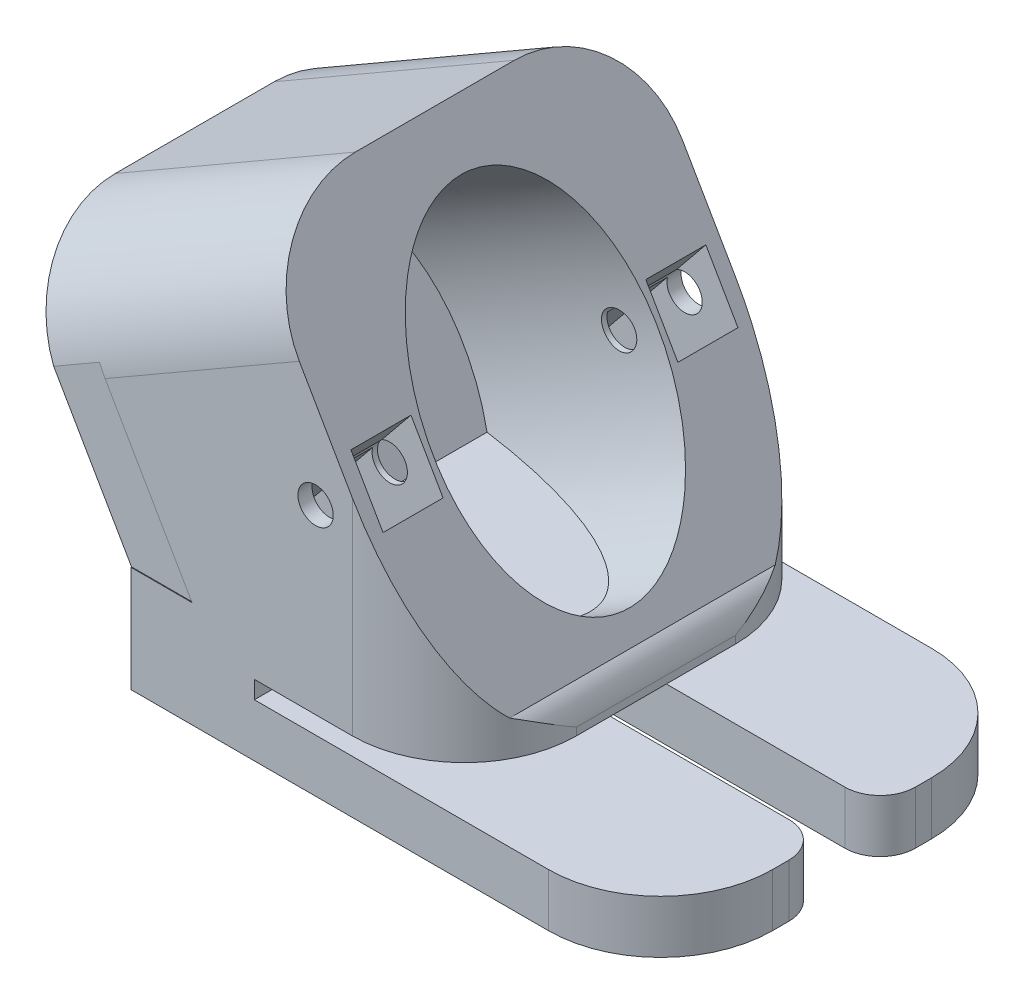
SolidWorks part; units mm, degrees
note: The reader was unsure of these and kept them because the rebuilt part matched: shared geometry of "Sketch7<3>".
ref_plane "Front Plane" through (0, 0, 0) normal (0, 0, 1) x (1, 0, 0)
ref_plane "Top Plane" through (0, 0, 0) normal (0, 1, 0) x (1, 0, 0)
ref_plane "Right Plane" through (0, 0, 0) normal (1, 0, 0) x (0, 0, -1)
sketch "Sketch1" plane through (0, 0, 0) normal (0, 0, 1) x (1, 0, 0)
  line L0 (0, 0) -> (16.4978, 9.525)
  line L1 (0, 0) -> (20.7767, 0) construction
  line L2 (12.7, 0) -> (19.6728, 4.0257)
  line L3 (19.6928, 3.9911) -> (16.4978, 9.525) construction
  point P9 (14.1735, 0.8507)
  dimension "D1" = 19.05
  dimension "D2" = 30
  dimension "D3" = 6.35
  dimension "D4" = 8.0515
  dimension "D5" = 6.35
ref_plane "Plane1" through (16.4978, 9.525, 0) normal (0.866, 0.5, 0) x (0, 0, -1)
sketch "Sketch2" plane through (16.4978, 9.525, 0) normal (0.866, 0.5, 0) x (0, 0, -1)
  line L0 (0, 100000) -> (0, -100010.3884) construction
  line L1 (10.85, 12.525) -> (10.85, -12.525)
  line L2 (10.85, 12.525) -> (-10.85, 12.525)
  line L3 (10.85, -12.525) -> (-10.85, -12.525)
  line L4 (-10.85, 12.525) -> (-10.85, -12.525)
  line L5 (10.85, 12.525) -> (-10.85, -12.525) construction
  line L6 (10.85, -12.525) -> (-10.85, 12.525) construction
  ellipse E0 centre (0, 0) end of major axis (0, 9.525) minor radius 6.35
  point P1 (-10.85, 0)
  point P7 (0, -12.525)
  dimension "D1" = 19.05
  dimension "D2" = 12.7
  dimension "D3" = 4.5
  dimension "D4" = 3
extrude "Boss-Extrude1" add sketch "Sketch2" against normal blind 12.7
sketch "Sketch3" plane through (5.4993, 3.175, 0) normal (-0.866, -0.5, 0) x (0, 0, 1)
  line L0 (-10.85, 12.525) -> (-10.85, -12.525)
  line L1 (-10.85, 12.525) -> (10.8107, 12.525)
  line L2 (-10.85, -12.525) -> (10.8107, -12.525)
  line L3 (10.8107, 12.525) -> (10.8107, -12.525)
extrude "Boss-Extrude2" add sketch "Sketch3" along normal blind 3
sketch "Sketch5" plane through (0, 0, 0) normal (0, 1, 0) x (-1, 0, 0)
  line L0 (-22.7603, 10.85) -> (-22.7603, -10.85)
  line L1 (-22.7603, 10.85) -> (-3.8682, 10.85)
  line L2 (-22.7603, -10.85) -> (-3.8682, -10.85)
  line L3 (-3.8682, 10.85) -> (-3.8682, -10.85)
  line L8 (-22.7603, 10.85) -> (-22.7603, -10.85) construction
extrude "Boss-Extrude3" add sketch "Sketch5" against normal blind 2
sketch "Sketch6" plane through (0, -2, 0) normal (0, -1, 0) x (1, 0, 0)
  line L0 (3.8682, -10.85) -> (3.8682, 10.85)
  line L1 (3.8682, -10.85) -> (33.8682, -10.85)
  line L2 (3.8682, 10.85) -> (33.8682, 10.85)
  line L3 (33.8682, -10.85) -> (33.8682, 10.85)
  line L10 (3.8682, 10.85) -> (8.487, 10.85) construction
  line L11 (3.8682, -10.85) -> (3.8682, 10.85) construction
  dimension "D1" = 30
extrude "Boss-Extrude4" add sketch "Sketch6" along normal blind 4
sketch "Sketch7" plane through (33.8682, 0, 0) normal (1, 0, 0) x (0, 0, -1)
  line L0 (-10.85, -2) -> (10.85, -2)
  line L1 (-10.85, -2) -> (-10.85, -3)
  line L2 (10.85, -2) -> (10.85, -3)
  line L3 (-10.85, -3) -> (10.85, -3)
  line L4 (-1.5875, -3) -> (1.5875, -3)
  line L5 (-10.85, -6) -> (-10.85, -2) construction
  line L6 (-10.85, -6) -> (10.85, -6)
  line L7 (-10.85, -6) -> (-10.85, -13.2725)
  line L8 (10.85, -6) -> (10.85, -13.2725)
  line L9 (-10.85, -13.2725) -> (10.85, -13.2725)
  line L10 (-1.5875, -3) -> (-1.5875, -6)
  line L11 (1.5875, -3) -> (1.5875, -6)
  line L12 (-1.5875, -6) -> (1.5875, -6)
  point P0 (0, -3)
  point P11 (0, -3)
  line M4 (-10.85, -6) -> (10.85, -6)
  dimension "D1" = 1
  dimension "D2" = 3.175
extrude "Cut-Extrude2" cut sketch "Sketch7" against normal blind 23 contours L2 L3 L1 L0 | L10 L12 L11 L4
extrude "Cut-Extrude3" cut sketch "Sketch7<3>" against normal through all contours L7 L9 L8 M4
sketch "Sketch7<3>" plane through (33.8682, 0, 0) normal (1, 0, 0) x (0, 0, -1) same geometry as "Sketch7"
ref_plane "Plane2" through (3.175, -5.4993, 0) normal (0.5, -0.866, 0) x (0.866, 0.5, 0)
sketch "Sketch8" plane through (3.175, -5.4993, 6.35) normal (0.5, -0.866, 0) x (0.75, 0.433, -0.5)
  line L0 (13.7985, 1.5003) -> (14.5485, 0.2012)
  line L1 (13.7985, 1.5003) -> (-3.522, -8.4997)
  line L2 (14.5485, 0.2012) -> (-2.772, -9.7988)
  line L3 (-3.522, -8.4997) -> (-2.772, -9.7988)
  line L4 (12.7, 0) -> (19.6728, 4.0257) construction
  dimension "D1" = 1.5
  dimension "D2" = 20
ref_plane "Plane3" through (19.6728, 0, 0) normal (1, 0, 0) x (0, 0, -1)
sketch "Sketch11" plane through (19.6728, 0.1949, 0) normal (-1, 0, 0) x (0, 0, -1)
  circle A0 centre (0, -3.8309) radius 1
  dimension "D1" = 2
extrude "Cut-Extrude8" cut sketch "Sketch11" along normal through all
sketch "Sketch13" plane through (0, 0, 0) normal (0, 0, 1) x (1, 0, 0)
  line L0 (16.4978, 9.525) -> (3.8682, -6)
sketch "Sketch9" plane through (0, 0, -10.85) normal (0, 0, -1) x (-1, 0, 0)
  line L0 (0, 0) -> (-16.4978, 9.525) construction
  line L1 (-10.2353, 20.372) -> (-21.997, 0) construction
  circle A0 centre (-14.3327, 8.275) radius 1
  dimension "D1" = 2
  dimension "D2" = 2.5
extrude "Cut-Extrude4" cut sketch "Sketch9" against normal up to next contours A0
ref_plane "Plane4" through (16.4978, 9.525, 0) normal (0.6311, 0.7757, 0) x (0.7757, -0.6311, 0)
sketch "Sketch15" plane through (16.4978, 9.525, 0) normal (0.6311, 0.7757, 0) x (0.7757, -0.6311, 0)
  line L0 (-11.7031, -10.85) -> (10.2768, -10.85) construction
  line L1 (-1.8, -6.65) -> (1.6, -6.65)
  line L2 (-1.8, -6.65) -> (-1.8, -10.05)
  line L3 (-1.8, -10.05) -> (1.6, -10.05)
  line L4 (1.6, -6.65) -> (1.6, -10.05)
  line L5 (-0.8907, -8.6694) -> (-0.8907, 3.3485) construction
  line L6 (0, 0) -> (0, -5.6108) construction
  dimension "D1" = 3.4
  dimension "D2" = 1.6
  dimension "D3" = 0.8
  dimension "D4" = 1.8
  dimension "D5" = 2.4907
extrude "Cut-Extrude9" cut sketch "Sketch15" against normal through all both and the other way through all
mirror "Mirror1" about plane through (0, 0, 0) normal (0, 0, 1) of "Cut-Extrude4", "Cut-Extrude9"
fillet "Fillet5" radius 6.35 6 edges at (33.8682, -4.5, 10.85) (33.8682, -4.5, -10.85) (22.7603, -1, -10.85) (22.7603, -1, 10.85) (4.736, 17.197, 10.85) (3.437, 16.447, -10.85)
fillet "Fillet6" radius 2 2 edges at (33.8682, -4.5, -1.5875) (33.8682, -4.5, 1.5875)
fillet "Fillet7" radius 2 1 edges at (22.7603, 0, 0)
